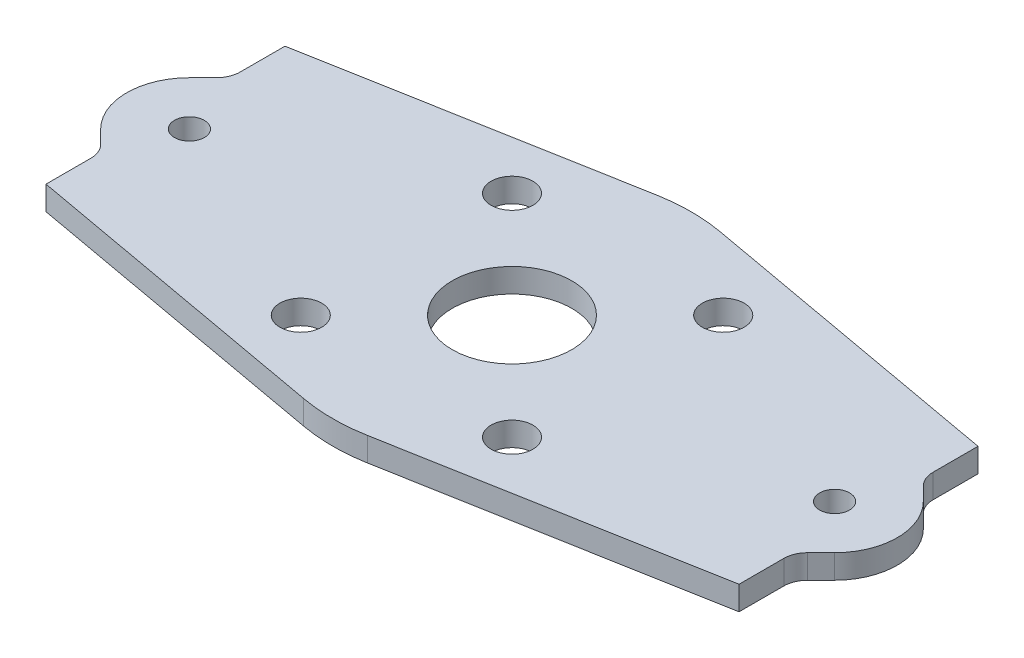
SolidWorks part; units mm, degrees
material "Hexcel AS4C (3000 Filaments)"
ref_plane "Front Plane" through (0, 0, 0) normal (0, 0, 1) x (1, 0, 0)
ref_plane "Top Plane" through (0, 0, 0) normal (0, 1, 0) x (1, 0, 0)
ref_plane "Right Plane" through (0, 0, 0) normal (1, 0, 0) x (0, 0, -1)
sketch "Sketch1" plane through (0, 0, 0) normal (0, 1, 0) x (1, 0, 0)
  line L0 (-2.6687, 14.7607) -> (-29, 10)
  line L1 (2.6687, 14.7607) -> (29, 10)
  line L2 (-2.6687, -14.7607) -> (-29, -10)
  line L4 (-29, 10) -> (-29, 6.253)
  line L11 (2.6687, -14.7607) -> (29, -10)
  line L12 (29, 10) -> (29, 6.253)
  line L13 (29, -10) -> (29, -6.253)
  line L14 (-30.7123, 3.7123) -> (-29.5858, 4.8388)
  line L16 (-30.7123, -3.7123) -> (-29.5858, -4.8388)
  line L17 (30.7123, 3.7123) -> (29.5858, 4.8388)
  line L18 (-29, -10) -> (-29, -6.253)
  line L19 (30.7123, -3.7123) -> (29.5858, -4.8388)
  circle A7 centre (0, 0) radius 5
  circle A8 centre (-27, 0) radius 1.25
  circle A9 centre (27, 0) radius 1.25
  circle A11 centre (8.8388, 8.8388) radius 1.75
  circle A12 centre (8.8388, -8.8388) radius 1.75
  circle A13 centre (-8.8388, -8.8388) radius 1.75
  circle A14 centre (-8.8388, 8.8388) radius 1.75
  arc A15 (-2.6687, 14.7607) -> (2.6687, 14.7607) centre (0, 0) cw
  arc A16 (2.6687, -14.7607) -> (-2.6687, -14.7607) centre (0, 0) cw
  circle A17 centre (-27, 0) radius 5.25
  circle A18 centre (27, 0) radius 5.25
  arc A19 (29, 6.253) -> (29.5858, 4.8388) centre (31, 6.253) ccw
  arc A20 (-29, 6.253) -> (-29.5858, 4.8388) centre (-31, 6.253) cw
  arc A21 (-29.5858, -4.8388) -> (-29, -6.253) centre (-31, -6.253) cw
  arc A22 (29.5858, -4.8388) -> (29, -6.253) centre (31, -6.253) ccw
  point P15 (0, 0)
  point P33 (0, 0)
  point P43 (-29, -5.4246)
  point P46 (29, -5.4246)
  dimension "D1" = 4
  dimension "D2" = 4
  dimension "D3" = 2
  dimension "D4" = 2
extrude "Boss-Extrude1" add sketch "Sketch1" along normal blind 2 contours A22 L19 A18 L17 A19 L12 L1 A15 L0 L4 A20 L14 A17 L16 A21 L18 L2 A16 L11 L13 A14 A13 A12 A11 A7 | A17 A8 | A18 A9 region at (0, 0, -14.3164) region at (-25.0477, 0, -4.7132) region at (31.7132, 0, -1.9523)
